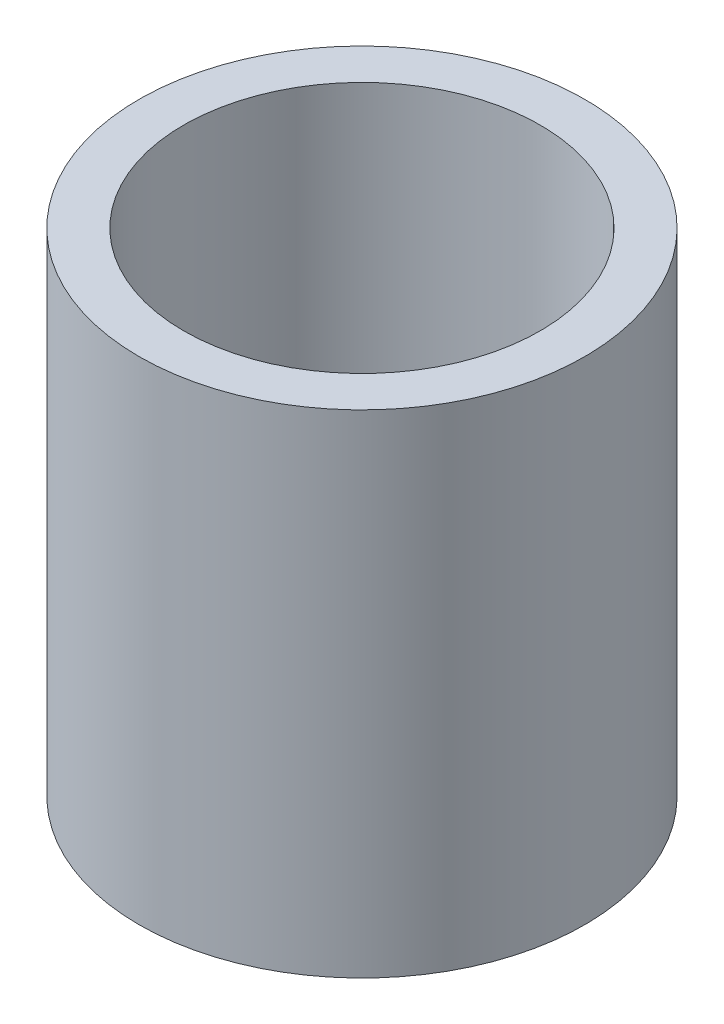
SolidWorks part; units mm, degrees
ref_plane "Front Plane" through (0, 0, 0) normal (0, 0, 1) x (1, 0, 0)
ref_plane "Top Plane" through (0, 0, 0) normal (0, 1, 0) x (1, 0, 0)
ref_plane "Right Plane" through (0, 0, 0) normal (1, 0, 0) x (0, 0, -1)
sketch "Sketch1" plane through (0, 0, 0) normal (0, 1, 0) x (1, 0, 0)
  circle A0 centre (0, 0) radius 15.875
  circle A1 centre (0, 0) radius 12.7
  dimension "D1" = 31.75
  dimension "D2" = 25.4
extrude "Boss-Extrude1" add sketch "Sketch1" along normal mid plane 35.052
